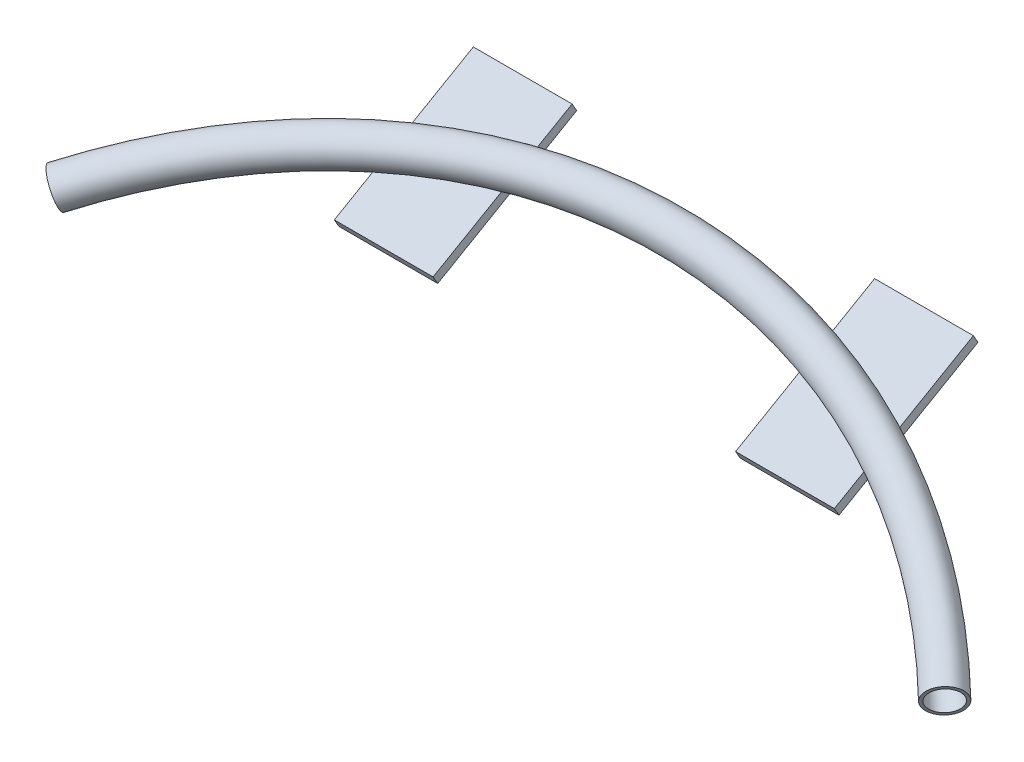
SolidWorks part; units mm, degrees
ref_plane "Front" through (0, 0, 0) normal (0, 0, 1) x (1, 0, 0)
ref_plane "Top" through (0, 0, 0) normal (0, 1, 0) x (1, 0, 0)
ref_plane "Right" through (0, 0, 0) normal (1, 0, 0) x (0, 0, -1)
sketch "Sketch4" plane through (0, 0, 0) normal (1, 0, 0) x (0, 0, -1)
  line L0 (0, 0) -> (175.9764, 101.6) construction
  line L1 (0, 0) -> (114.1912, 0) construction
  dimension "D1" = 203.2
  dimension "D2" = 101.6
  dimension "D3" = 30
ref_axis "Axis1" through (55.88, 0, 0) along (-1, 0, 0)
ref_plane "Plane3" through (0, 0, 0) normal (0, -0.866, -0.5) x (1, 0, 0)
sketch "Sketch5" plane through (0, 0, 0) normal (0, -0.866, -0.5) x (1, 0, 0)
  line L0 (-457.2, 0) -> (457.2, 0) construction
  line L4 (0, 0) -> (0, -203.2) construction
  arc A0 (-457.2, 0) -> (457.2, 0) centre (0, 412.75) ccw
  dimension "D1" = 914.4
  dimension "D2" = 203.2
ref_plane "Plane4" through (457.2, 0, 0) normal (0.6701, -0.3711, 0.6428) x (0.5623, -0.3114, -0.766)
sketch "Sketch6" plane through (457.2, 0, 0) normal (0.6701, -0.3711, 0.6428) x (0.5623, -0.3114, -0.766)
  circle A0 centre (0, 0) radius 19.05
  circle A1 centre (0, 0) radius 15.875
  dimension "D1" = 38.1
  dimension "D2" = 31.75
sweep "Sweep2" add profiles "Sketch6" path "Sketch5"
ref_plane "Plane5" through (0, -16.4978, -9.525) normal (0, -0.866, -0.5) x (1, 0, 0)
sketch "Sketch7" plane through (0, -16.4978, -9.525) normal (0, -0.866, -0.5) x (1, 0, 0)
  line L1 (-257.175, -88.9) -> (-155.575, -88.9)
  line L2 (-257.175, -88.9) -> (-257.175, -254)
  line L3 (-257.175, -254) -> (-155.575, -254)
  line L4 (-155.575, -88.9) -> (-155.575, -254)
  line L5 (155.575, -88.9) -> (257.175, -88.9)
  line L6 (155.575, -88.9) -> (155.575, -254)
  line L7 (155.575, -254) -> (257.175, -254)
  line L8 (257.175, -88.9) -> (257.175, -254)
  line L10 (0, 0) -> (0, -312.0709) construction
  line L11 (55.88, 0) -> (-55.88, 0) construction
  dimension "D1" = 101.6
  dimension "D2" = 165.1
  dimension "D3" = 514.35
  dimension "D4" = 88.9
extrude "Extrude1" add sketch "Sketch7" along normal blind 9.525
